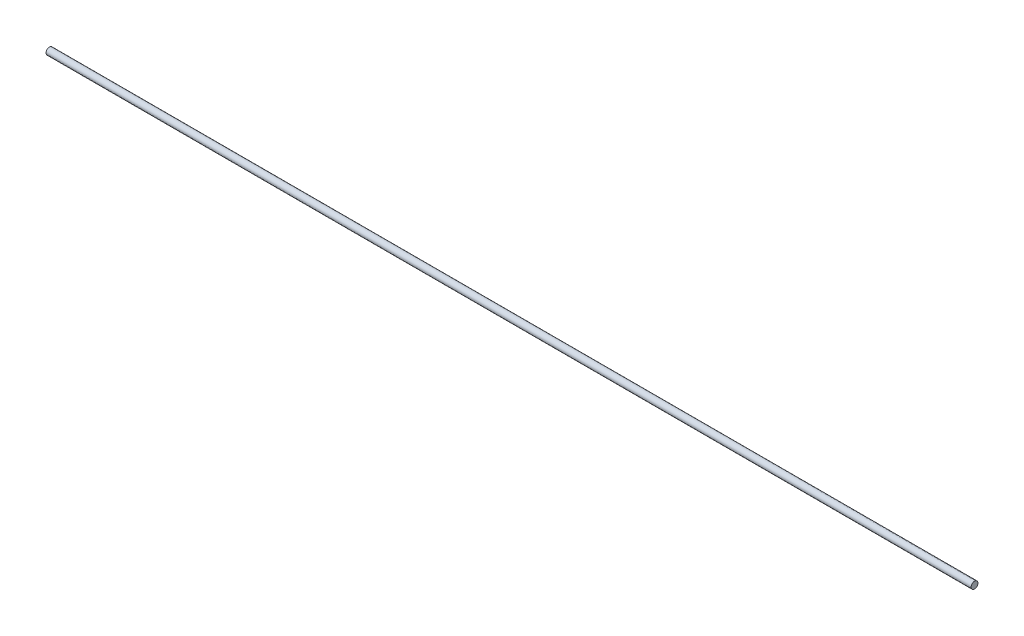
SolidWorks part; units mm, degrees
material "Hexcel AS4C (3000 Filaments)"
ref_plane "Front Plane" through (0, 0, 0) normal (0, 0, 1) x (1, 0, 0)
ref_plane "Top Plane" through (0, 0, 0) normal (0, 1, 0) x (1, 0, 0)
ref_plane "Right Plane" through (0, 0, 0) normal (1, 0, 0) x (0, 0, -1)
sketch "Sketch1" plane through (0, 0, 0) normal (1, 0, 0) x (0, 0, -1)
  circle A1 centre (4.7956, 16.2262) radius 3
extrude "Boss-Extrude1" add sketch "Sketch1" along normal blind 812.8 contours A1
